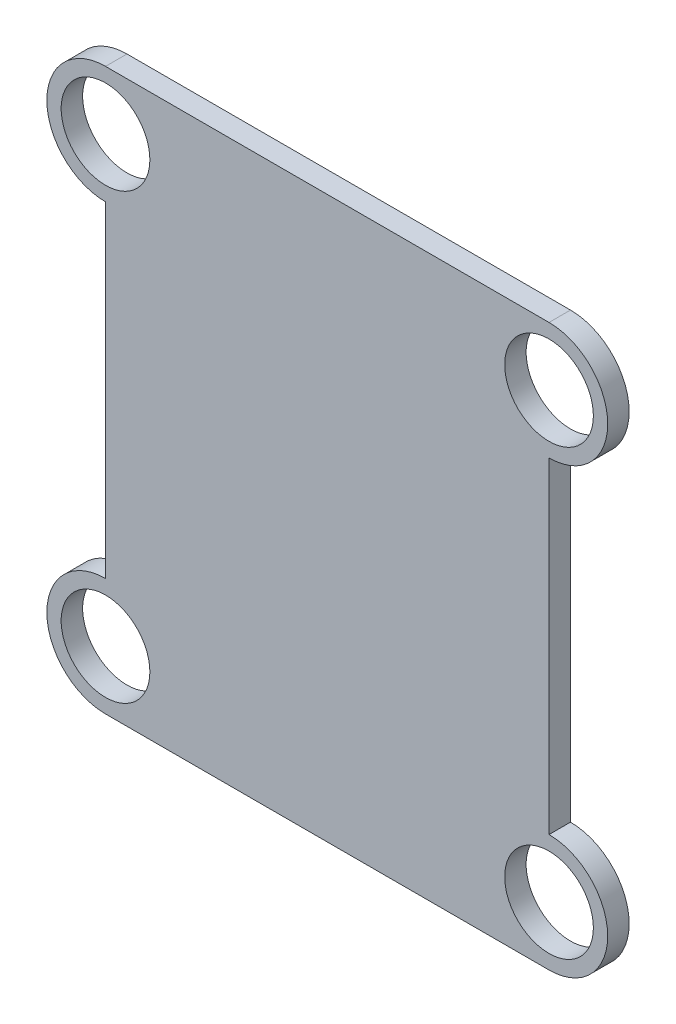
SolidWorks part; units mm, degrees
ref_plane "Front Plane" through (0, 0, 0) normal (0, 0, 1) x (1, 0, 0)
ref_plane "Top Plane" through (0, 0, 0) normal (0, 1, 0) x (1, 0, 0)
ref_plane "Right Plane" through (0, 0, 0) normal (1, 0, 0) x (0, 0, -1)
sketch "Sketch1" plane through (0, 0, 0) normal (0, 0, 1) x (1, 0, 0)
  line L0 (15.5, 19.6) -> (-15.5, 19.6)
  line L1 (15.5, 11.4) -> (15.5, -11.4)
  line L2 (-15.5, 11.4) -> (-15.5, -11.4)
  line L3 (-15.5, -19.6) -> (15.5, -19.6)
  circle A0 centre (15.5, -15.5) radius 3.1 construction
  circle A1 centre (-15.5, -15.5) radius 3.1 construction
  circle A2 centre (15.5, 15.5) radius 3.1 construction
  circle A3 centre (-15.5, 15.5) radius 3.1 construction
  circle A4 centre (15.5, 15.5) radius 4.1 construction
  circle A5 centre (15.5, -15.5) radius 4.1 construction
  circle A6 centre (-15.5, 15.5) radius 4.1 construction
  circle A7 centre (-15.5, -15.5) radius 4.1 construction
  circle A8 centre (15.5, 15.5) radius 3.1
  arc A9 (15.5, 19.6) -> (15.5, 11.4) centre (15.5, 15.5) cw
  circle A10 centre (15.5, -15.5) radius 3.1
  arc A11 (-15.5, 19.6) -> (-15.5, 11.4) centre (-15.5, 15.5) ccw
  circle A12 centre (-15.5, -15.5) radius 3.1
  arc A13 (15.5, -11.4) -> (15.5, -19.6) centre (15.5, -15.5) cw
  circle A14 centre (-15.5, 15.5) radius 3.1
  arc A15 (-15.5, -11.4) -> (-15.5, -19.6) centre (-15.5, -15.5) ccw
  point P0 (-15.5, -15.5)
  point P1 (-15.5, 15.5)
  point P2 (15.5, 15.5)
  point P3 (15.5, -15.5)
  dimension "D8" = 6.2
  dimension "DIA_TOP" = 6.2
  dimension "D9" = 6.2
  dimension "D10" = 6.2
  dimension "D11" = 8.2
  dimension "D12" = 8.2
  dimension "D13" = 8.2
  dimension "D14" = 8.2
  dimension "D1" = 15.5
  dimension "HALF_DIST" = 15.5
  dimension "D2" = 15.5
  dimension "D3" = 15.5
  dimension "D4" = 15.5
  dimension "D5" = 15.5
  dimension "D6" = 15.5
  dimension "D7" = 15.5
extrude "Extrude1" add sketch "Sketch1" along normal blind 1.5
equation "\"D2@Sketch1\" = \"HALF_DIST\""
equation "\"D3@Sketch1\" = \"HALF_DIST\""
equation "\"D1@Sketch1\" = \"HALF_DIST\""
equation "\"D4@Sketch1\" = \"HALF_DIST\""
equation "\"D5@Sketch1\" = \"HALF_DIST\""
equation "\"D6@Sketch1\" = \"HALF_DIST\""
equation "\"D7@Sketch1\" = \"HALF_DIST\""
equation "\"D8@Sketch1\" = \"DIA_TOP\""
equation "\"D9@Sketch1\" = \"DIA_TOP\""
equation "\"D10@Sketch1\" = \"DIA_TOP\""
equation "\"D11@Sketch1\" = \"DIA_TOP\"+2"
equation "\"D12@Sketch1\" = \"DIA_TOP\"+2"
equation "\"D13@Sketch1\" = \"DIA_TOP\"+2"
equation "\"D14@Sketch1\" = \"DIA_TOP\"+2"
